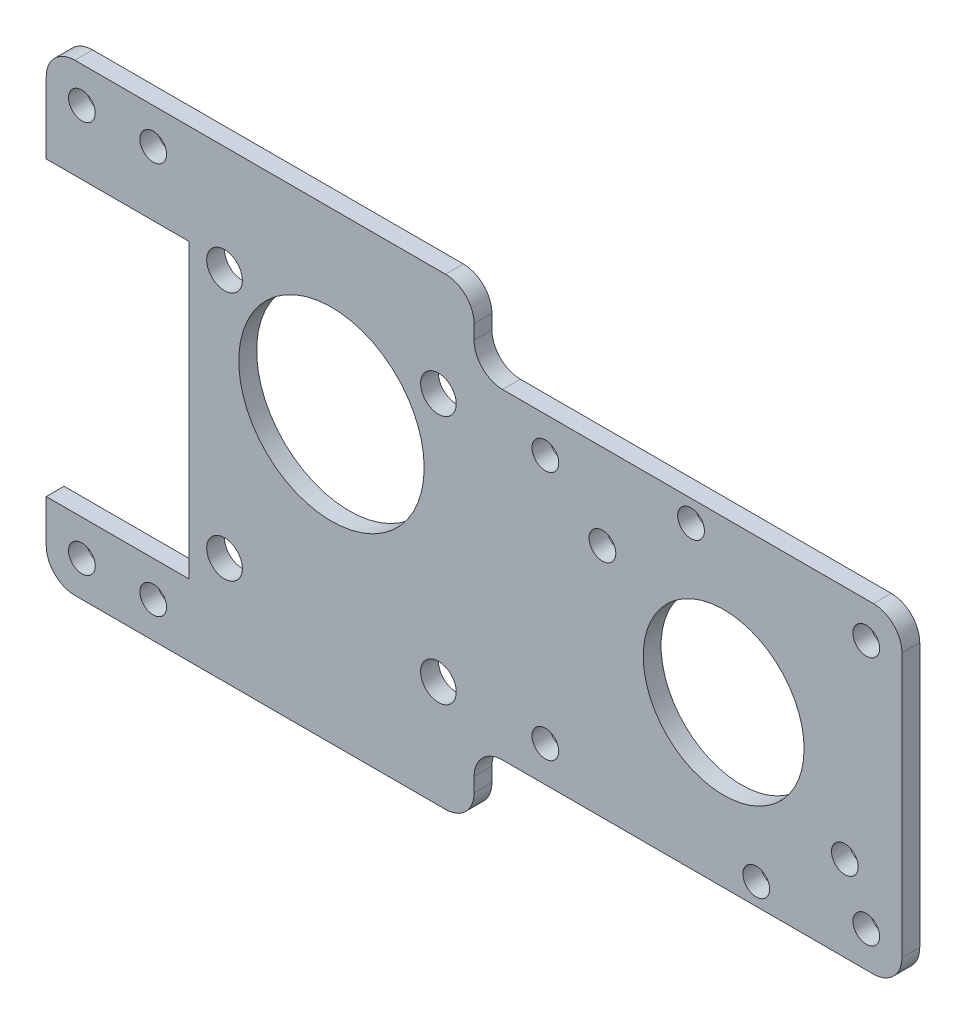
SolidWorks part; units mm, degrees
material "6061-T6 (SS)"
ref_plane "Front Plane" through (0, 0, 0) normal (0, 0, 1) x (1, 0, 0)
ref_plane "Top Plane" through (0, 0, 0) normal (0, 1, 0) x (1, 0, 0)
ref_plane "Right Plane" through (0, 0, 0) normal (1, 0, 0) x (0, 0, -1)
sketch "Sketch1" plane through (0, 0, 0) normal (0, 0, 1) x (1, 0, 0)
  line L1 (-63.5, 28.575) -> (63.5, 28.575)
  line L2 (-63.5, 28.575) -> (-63.5, -28.575)
  line L3 (-63.5, -28.575) -> (63.5, -28.575)
  line L4 (63.5, 28.575) -> (63.5, -28.575)
  line L5 (-63.5, 28.575) -> (63.5, -28.575) construction
  line L6 (-63.5, -28.575) -> (63.5, 28.575) construction
  circle A0 centre (31.75, 0) radius 14.3256
  circle A1 centre (31.75, 0) radius 25.4 construction
  circle A2 centre (37.5551, -24.7277) radius 2.3812
  circle A3 centre (18.3697, -21.59) radius 2.3813
  circle A4 centre (7.0223, -5.8051) radius 2.3813
  circle A5 centre (10.16, 13.3803) radius 2.3813
  circle A6 centre (25.9449, 24.7277) radius 2.3813
  circle A7 centre (45.1303, 21.59) radius 2.3812
  circle A8 centre (56.4777, 5.8051) radius 2.3812
  circle A9 centre (53.34, -13.3803) radius 2.3812
  point P0 (0, 0)
  point P27 (31.75, 0)
  dimension "D3" = 28.6512
  dimension "D5" = 50.8
  dimension "D8" = 4.7625
  dimension "D1" = 127
  dimension "D2" = 57.15
  dimension "D4" = 31.75
  dimension "D7" = 21.59
  dimension "D6" = 8
extrude "Boss-Extrude1" add sketch "Sketch1" along normal blind 3.175 contours A8 L4 L1 L2 L3 A9 A7 A6 A5 A4 A3 A2 A0 | L4 A8 | A3 | A4 | A7 region at (-3.8627, 0, 0) region at (18.3697, -21.59, 0) region at (7.0223, -5.8051, 0) region at (45.1303, 21.59, 0) region at (56.4777, 5.8051, 0)
sketch "Sketch2" plane through (0, 0, 3.175) normal (0, 0, 1) x (1, 0, 0)
  line L0 (-63.5, 28.575) -> (63.5, 28.575) construction
  line L1 (63.5, 28.575) -> (63.5, -28.575) construction
  line L2 (-63.5, -28.575) -> (63.5, -28.575) construction
  circle A0 centre (57.15, 22.225) radius 2.3812
  circle A1 centre (57.15, -22.225) radius 2.3812
  circle A2 centre (0, 22.225) radius 2.3813
  circle A3 centre (0, -22.225) radius 2.3813
  dimension "D1" = 4.7625
  dimension "D4" = 4.7625
  dimension "D7" = 4.7625
  dimension "D8" = 4.7625
  dimension "D2" = 6.35
  dimension "D3" = 6.35
  dimension "D5" = 6.35
  dimension "D6" = 6.35
  dimension "D9" = 57.15
  dimension "D10" = 57.15
  dimension "D11" = 6.35
  dimension "D12" = 6.35
extrude "Cut-Extrude1" cut sketch "Sketch2" against normal blind 3.175
fillet "Fillet1" radius 5.08 2 edges at (63.5, -28.575, 1.5875) (63.5, 28.575, 1.5875)
sketch "Sketch3" plane through (0, 0, 3.175) normal (0, 0, 1) x (1, 0, 0)
  line L0 (-63.5, 28.575) -> (-63.5, -28.575) construction
  line L1 (-63.5, 28.575) -> (58.42, 28.575) construction
  line L2 (-63.5, 0) -> (63.5, 0) construction
  line L3 (63.5, 23.495) -> (63.5, -23.495) construction
  circle A0 centre (-57.15, 22.225) radius 3.175
  circle A1 centre (-19.05, 22.225) radius 3.175
  circle A2 centre (-19.05, -22.225) radius 3.175
  circle A3 centre (-57.15, -22.225) radius 3.175
  dimension "D3" = 6.35
  dimension "D4" = 6.35
  dimension "D1" = 6.35
  dimension "D2" = 6.35
  dimension "D5" = 38.1
extrude "Cut-Extrude2" cut sketch "Sketch3" against normal blind 3.175
sketch "Sketch4" plane through (0, 0, 3.175) normal (0, 0, 1) x (1, 0, 0)
  line L0 (-63.5, 28.575) -> (58.42, 28.575) construction
  line L1 (-63.5, 28.575) -> (-63.5, -28.575) construction
  circle A0 centre (-38.1, 9.525) radius 16.51
  dimension "D1" = 33.02
  dimension "D2" = 19.05
  dimension "D3" = 25.4
extrude "Cut-Extrude3" cut sketch "Sketch4" against normal blind 7.62
sketch "Sketch5" plane through (0, 0, 3.175) normal (0, 0, 1) x (1, 0, 0)
  line L0 (-63.5, -28.575) -> (58.42, -28.575) construction
  line L1 (-12.7, -28.575) -> (-88.9, -28.575)
  line L2 (-12.7, -28.575) -> (-12.7, -41.275)
  line L3 (-12.7, -41.275) -> (-88.9, -41.275)
  line L4 (-88.9, -28.575) -> (-88.9, -41.275)
  line L5 (-63.5, 28.575) -> (-63.5, -28.575) construction
  line L6 (-63.5, 28.575) -> (58.42, 28.575) construction
  line L7 (-12.7, 28.575) -> (-88.9, 28.575)
  line L8 (-12.7, 28.575) -> (-12.7, 41.275)
  line L9 (-12.7, 41.275) -> (-88.9, 41.275)
  line L10 (-88.9, 28.575) -> (-88.9, 41.275)
  dimension "D1" = 50.8
  dimension "D2" = 12.7
  dimension "D3" = 25.4
  dimension "D4" = 12.7
  dimension "D5" = 25.4
  dimension "D6" = 50.8
extrude "Boss-Extrude2" add sketch "Sketch5" against normal blind 3.175
fillet "Fillet2" radius 5.08 4 edges at (-12.7, -41.275, 1.5875) (-12.7, -28.575, 1.5875) (-12.7, 41.275, 1.5875) (-12.7, 28.575, 1.5875)
sketch "Sketch6" plane through (0, 0, 3.175) normal (0, 0, 1) x (1, 0, 0)
  line L0 (-88.9, 41.275) -> (-88.9, 28.575) construction
  line L1 (-63.5, 28.575) -> (-88.9, 28.575)
  line L2 (-63.5, 28.575) -> (-63.5, 23.495)
  line L3 (-63.5, 23.495) -> (-88.9, 23.495)
  line L4 (-88.9, 28.575) -> (-88.9, 23.495)
  line L5 (-63.5, -28.575) -> (-88.9, -28.575) construction
  dimension "D1" = 52.07
extrude "Boss-Extrude3" add sketch "Sketch6" against normal blind 3.175
fillet "Fillet3" radius 5.08 2 edges at (-88.9, 41.275, 1.5875) (-88.9, -41.275, 1.5875)
sketch "Sketch7" plane through (0, 0, 3.175) normal (0, 0, 1) x (1, 0, 0)
  line L0 (-88.9, -28.575) -> (-88.9, -36.195) construction
  line L1 (-88.9, 36.195) -> (-88.9, 23.495) construction
  line L2 (-83.82, -41.275) -> (-17.78, -41.275) construction
  line L3 (-17.78, 41.275) -> (-83.82, 41.275) construction
  line L4 (-17.78, 41.275) -> (-83.82, 41.275) construction
  circle A0 centre (-82.55, 34.925) radius 2.3813
  circle A1 centre (-82.55, -34.925) radius 2.3813
  circle A2 centre (-69.85, 34.925) radius 2.3813
  circle A3 centre (-69.85, -34.925) radius 2.3813
  dimension "D1" = 4.7625
  dimension "D2" = 4.7625
  dimension "D7" = 4.7625
  dimension "D8" = 4.7625
  dimension "D3" = 6.35
  dimension "D4" = 6.35
  dimension "D5" = 6.35
  dimension "D6" = 6.35
  dimension "D9" = 6.35
  dimension "D10" = 6.35
  dimension "D11" = 12.7
  dimension "D12" = 12.7
extrude "Cut-Extrude4" cut sketch "Sketch7" against normal blind 3.175
